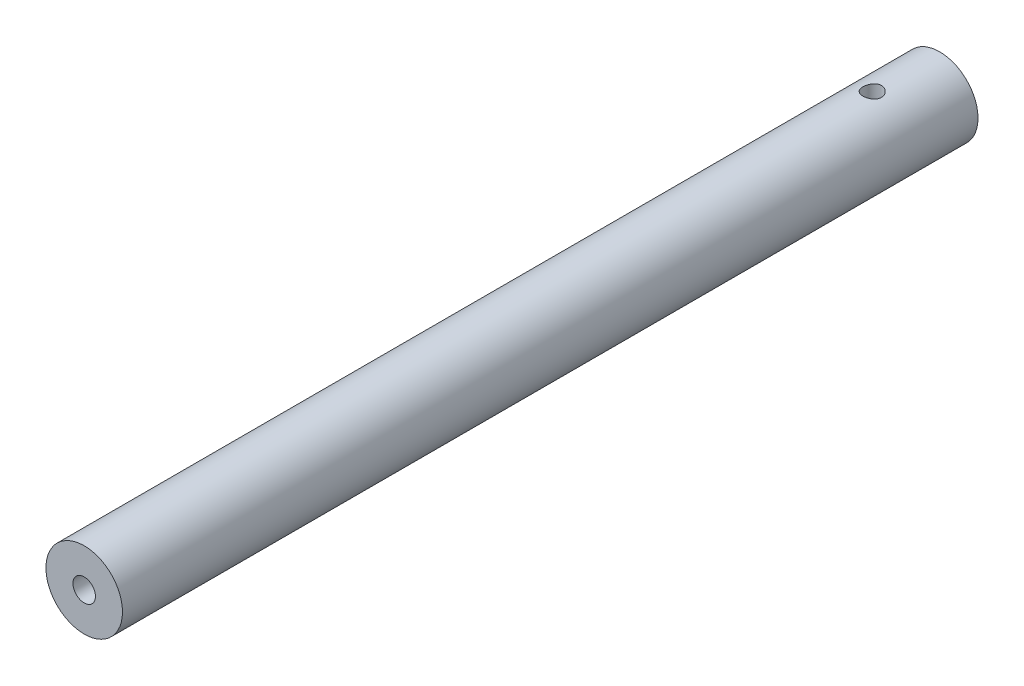
SolidWorks part; units mm, degrees
ref_plane "Front Plane" through (0, 0, 0) normal (0, 0, 1) x (1, 0, 0)
ref_plane "Top Plane" through (0, 0, 0) normal (0, 1, 0) x (1, 0, 0)
ref_plane "Right Plane" through (0, 0, 0) normal (1, 0, 0) x (0, 0, -1)
sketch "Sketch1" plane through (0, 0, 0) normal (0, 0, 1) x (1, 0, 0)
  circle A0 centre (0, 0) radius 10.795
  circle A1 centre (0, 0) radius 3.175
  dimension "D1" = 21.59
  dimension "D2" = 6.35
extrude "Boss-Extrude1" add sketch "Sketch1" along normal blind 241.3
sketch "Sketch2" plane through (0, 0, 0) normal (0, 1, 0) x (1, 0, 0)
  line L0 (10.795, 0) -> (-10.795, 0) construction
  circle A0 centre (0, -19.05) radius 2.6035
  dimension "D1" = 5.207
  dimension "D2" = 19.05
extrude "Cut-Extrude1" cut sketch "Sketch2" against normal blind 254 and the other way blind 254
